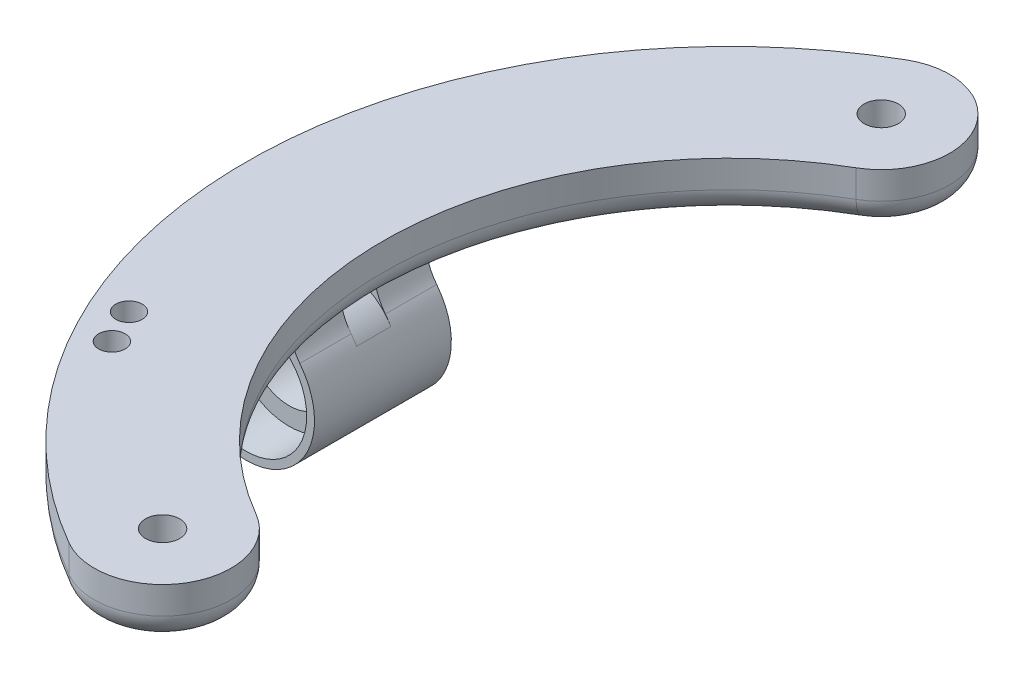
SolidWorks part; units mm, degrees
ref_plane "Front Plane" through (0, 0, 0) normal (0, 0, 1) x (1, 0, 0)
ref_plane "Top Plane" through (0, 0, 0) normal (0, 1, 0) x (1, 0, 0)
ref_plane "Right Plane" through (0, 0, 0) normal (1, 0, 0) x (0, 0, -1)
sketch "Sketch1" plane through (0, 0, 0) normal (0, 0, 1) x (1, 0, 0)
  line L0 (0, -6.6146) -> (0, 6.6146) construction
  line L1 (-64.2938, 0) -> (-64.2938, -5.08)
  line L2 (-69.0563, -9.8425) -> (-84.9312, -9.8425)
  line L3 (-89.6937, -5.08) -> (-89.6937, 0)
  line L4 (-89.6937, 0) -> (-64.2938, 0)
  line L5 (64.4709, -12.0559) -> (-64.2938, -9.8425) construction
  arc A0 (-84.9312, -9.8425) -> (-89.6937, -5.08) centre (-84.9312, -5.08) cw
  arc A1 (-69.0563, -9.8425) -> (-64.2938, -5.08) centre (-69.0563, -5.08) ccw
  point P4 (0, 0)
  point P12 (-89.6937, -9.8425)
  dimension "D4" = 4.7625
  dimension "D1" = 25.4
  dimension "D2" = 9.8425
  dimension "D3" = 128.5875
revolve "MainAttachmentRing" add sketch "Sketch1" angle 360 about L0
sketch "Sketch2" plane through (0, 0, 0) normal (0, 0, 1) x (1, 0, 0)
  line L5 (-76.9938, -9.8425) -> (-76.9938, -22.5425) construction
  line L6 (-76.9938, -22.5425) -> (-76.9938, -39.878) construction
  line L7 (0, 0) -> (0, -9.8425) construction
  line L8 (0, -9.8425) -> (-76.9938, -9.8425) construction
  line L9 (-69.0563, -8.7943) -> (-69.0563, -3.4925)
  line L10 (-69.0563, -9.8425) -> (-84.9312, -9.8425) construction
  line L11 (-84.9312, -8.7943) -> (-84.9312, -3.4925)
  line L13 (-69.0563, -9.8425) -> (69.0563, -9.8425) construction
  line L14 (-69.0563, -9.8425) -> (69.0563, -9.8425) construction
  line L18 (-84.9312, -9.8425) -> (84.9312, -9.8425) construction
  line L19 (-84.9312, -9.8425) -> (84.9312, -9.8425) construction
  line L20 (-69.0563, -3.4925) -> (-84.9312, -3.4925)
  line L21 (-84.9312, -31.9405) -> (-84.9312, -24.325) construction
  line L22 (-84.9312, -24.325) -> (-84.9312, -23.2606) construction
  line L24 (-69.0563, -24.325) -> (-69.0563, -23.2606) construction
  line L25 (-84.9312, -23.2606) -> (-84.9312, -12.6286) construction
  line L26 (-69.0563, -23.2606) -> (-69.0563, -12.6286) construction
  circle A2 centre (-76.9938, -22.5425) radius 2.3813 construction
  arc A5 (-86.9723, -14.6864) -> (-67.0152, -14.6864) centre (-76.9938, -22.5425) ccw
  circle A6 centre (-76.9938, -22.5425) radius 8.1352 construction
  arc A7 (-69.0563, -12.6286) -> (-76.9938, -9.8425) centre (-76.9938, -22.5425) ccw construction
  circle A8 centre (-76.9938, -22.5425) radius 7.9375
  arc A9 (-76.9938, -9.8425) -> (-84.9312, -12.6286) centre (-76.9938, -22.5425) ccw construction
  arc A10 (-69.0563, -8.7943) -> (-67.0152, -14.6864) centre (-59.5313, -8.7943) ccw
  arc A11 (-84.9312, -8.7943) -> (-86.9723, -14.6864) centre (-94.4562, -8.7943) cw
  circle A12 centre (-76.9938, -22.5425) radius 4 construction
  dimension "D3" = 15.875
  dimension "D4" = 4.7625
  dimension "D6" = 9.525
  dimension "D5" = 8
  dimension "D7" = 12.7
  dimension "D1" = 6.35
  dimension "D2" = 12.7
extrude "SensorArmature" add sketch "Sketch2" along normal blind 12.7 and the other way blind 12.7 contours L11 A11 A5 A10 L9 L20 A12 region at (-68.9157, -12.0452, 0)
sketch "Sketch15" plane through (0, 0, 12.7) normal (0, 0, 1) x (1, 0, 0)
  circle A0 centre (-76.9938, -22.5425) radius 11.25
  dimension "D1" = 22.5
extrude "BearingRace1" cut sketch "Sketch15" against normal blind 8
sketch "Sketch16" plane through (0, 0, -12.7) normal (0, 0, -1) x (-1, 0, 0)
  circle A0 centre (76.9938, -22.5425) radius 11.25 construction
  circle A1 centre (76.9938, -22.5425) radius 11.25
extrude "BearingRace2" cut sketch "Sketch16" against normal blind 8
sketch "Sketch6" plane through (0, 0, 0) normal (0, 1, 0) x (1, 0, 0)
  line L0 (0, 0) -> (38.4252, 0) construction
  line L1 (68.0638, -50.8) -> (128.8023, -50.8)
  line L2 (66.0722, 0) -> (128.8023, 0) construction
  line L3 (66.0722, -53.3646) -> (66.0722, -20.0805)
  line L4 (68.0638, 50.8) -> (128.8023, 50.8)
  line L5 (128.8023, -50.8) -> (128.8023, 50.8)
  line L6 (66.0722, -20.0805) -> (66.0722, 0) construction
  line L7 (66.0722, 20.0805) -> (66.0722, 53.3646)
  line L8 (66.0722, 0) -> (66.0722, 20.0805) construction
  line L9 (66.0722, 53.3646) -> (66.0722, 60.6583) construction
  line L10 (66.0722, -60.6583) -> (66.0722, -53.3646) construction
  circle A0 centre (0, 0) radius 69.0563 construction
  circle A1 centre (0, 0) radius 89.6937 construction
  arc A2 (66.0722, -20.0805) -> (66.0722, 20.0805) centre (0, 0) ccw
  arc A3 (0, 69.0563) -> (66.0722, -20.0805) centre (0, 0) ccw construction
  arc A4 (66.0722, 20.0805) -> (0, 69.0563) centre (0, 0) ccw construction
  circle A5 centre (0, 0) radius 84.9312 construction
  arc A6 (68.0638, -50.8) -> (66.0722, -53.3646) centre (0, 0) ccw
  arc A7 (84.9312, 0) -> (66.0722, 53.3646) centre (0, 0) ccw construction
  arc A8 (66.0722, 53.3646) -> (68.0638, 50.8) centre (0, 0) ccw
  arc A9 (66.0722, -53.3646) -> (84.9312, 0) centre (0, 0) ccw construction
  arc A10 (0, 84.9312) -> (68.0638, -50.8) centre (0, 0) ccw construction
  arc A11 (68.0638, 50.8) -> (0, 84.9312) centre (0, 0) ccw construction
  dimension "D1" = 101.6
  dimension "D2" = 63.5
sketch "Sketch17" plane through (65.0875, 22.225, 0) normal (-1, 0, 0) x (0, 0, 1)
  line L0 (2.8259, -32.0675) -> (3.175, -32.0675)
  line L1 (3.175, -32.0675) -> (3.175, -33.655)
  line L2 (3.175, -33.655) -> (-3.175, -33.655)
  line L3 (-3.175, -33.655) -> (-3.175, -32.0675)
  line L4 (-3.175, -32.0675) -> (-2.8259, -32.0675)
  spline S0 degree 3 poles (-1002.8259, -32.0675) (-334.276, -32.0675) (334.2739, -32.0675) (1002.8237, -32.0675) knots -176.932162 -176.932162 -176.932162 -176.932162 177.931775 177.931775 177.931775 177.931775 only from (-2.8259, -32.0675) to (2.8259, -32.0675) construction
  spline S1 degree 3 poles (-2.8259, -32.0675) (-0.942, -32.0675) (0.942, -32.0675) (2.8259, -32.0675) knots 0 0 0 0 1 1 1 1
  dimension "D1" = 1.5875
  dimension "D2" = 6.35
extrude "Cut-Extrude3" cut sketch "Sketch17" along normal through all
fillet "Fillet1" radius 9.525 2 edges at (-85.3032, -11.43, 0) (-68.6843, -11.43, 0)
sketch "Sketch19" plane through (0, -9.8425, 0) normal (0, -1, 0) x (1, 0, 0)
  line L0 (-76.4874, 12.7) -> (-76.4874, -12.7) construction
  line L1 (-83.9763, 12.7) -> (-68.9984, 12.7) construction
  line L2 (-83.9763, -12.7) -> (-68.9984, -12.7) construction
  line L3 (-83.9763, 12.7) -> (-68.9984, 12.7) construction
  line L4 (-83.9763, 15.875) -> (-68.9984, 15.875)
  line L5 (-83.9763, 28.575) -> (-78.6026, 28.575)
  line L6 (-76.4874, 15.875) -> (-76.4874, 28.575) construction
  line L7 (-83.9763, 15.875) -> (-83.9763, 28.575)
  line L8 (-68.9984, 23.6461) -> (-68.9984, 15.875)
  line L9 (-68.9984, 28.575) -> (-68.9984, 24.7775) construction
  line L10 (-70.9492, 28.575) -> (-68.9984, 28.575) construction
  line L11 (-83.9763, 28.575) -> (-68.9984, 28.575) construction
  line L12 (-74.361, 28.575) -> (-70.9492, 28.575) construction
  circle A0 centre (0, 0) radius 76.4874 construction
  arc A1 (-62.0003, 39.1237) -> (-67.3705, 42.5124) centre (-64.6854, 40.818) ccw
  arc A2 (-67.3705, 42.5124) -> (-72.7997, 32.3466) centre (0, 0) ccw
  arc A3 (-62.0003, 39.1237) -> (-68.5893, 25.8884) centre (0, 0) ccw
  arc A4 (-78.6435, 12.7) -> (-67.3705, 42.5124) centre (0, 0) ccw construction
  circle A5 centre (0, 0) radius 79.6624 construction
  arc A6 (-72.204, 12.7) -> (-62.0003, 39.1237) centre (0, 0) ccw construction
  circle A7 centre (0, 0) radius 73.3124 construction
  arc A8 (-68.9984, 24.7775) -> (-71.573, 15.875) centre (0, 0) ccw construction
  arc A9 (-71.573, 15.875) -> (-72.204, 12.7) centre (0, 0) ccw construction
  arc A10 (-74.361, 28.575) -> (-76.4874, 22.266) centre (0, 0) ccw construction
  arc A11 (-76.4874, 22.266) -> (-78.0646, 15.875) centre (0, 0) ccw construction
  arc A12 (-78.0646, 15.875) -> (-78.6435, 12.7) centre (0, 0) ccw construction
  arc A13 (-66.3237, 38.0983) -> (-62.0003, 39.1237) centre (-64.6854, 40.818) ccw construction
  arc A14 (-67.3705, 42.5124) -> (-66.3237, 38.0983) centre (-64.6854, 40.818) ccw construction
  arc A15 (-72.7997, 32.3466) -> (-78.6026, 28.575) centre (-78.6026, 34.925) cw
  arc A16 (-68.5893, 25.8884) -> (-68.9984, 23.6461) centre (-62.6484, 23.6461) ccw
  point P9 (-76.4874, 0)
  dimension "D3" = 6.35
  dimension "D6" = 6.35
  dimension "D8" = 152.9748
  dimension "D7" = 28.118
  dimension "D1" = 3.175
  dimension "D2" = 12.7
  dimension "D4" = 3.175
  dimension "D5" = 3.175
extrude "MainSensorInset" cut sketch "Sketch19" against normal blind 6.35
hole_wizard "#10 (0.1935) Diameter Hole1" positions "Sketch25" profile "Sketch24" hole size "#10" standard "ANSI Inch" end condition through all
sketch "Sketch25" plane through (0, -9.8425, 0) normal (0, -1, 0) x (-1, 0, 0)
  line L0 (83.9763, -28.575) -> (83.9763, -15.875) construction
  line L1 (83.9763, -28.575) -> (83.9763, -15.875) construction
  line L2 (83.9763, -15.875) -> (68.9984, -15.875) construction
  line L3 (83.9763, -15.875) -> (68.9984, -15.875) construction
  line L4 (76.4874, -15.875) -> (76.4874, -34.925) construction
  line L6 (83.9763, -28.575) -> (76.4874, -28.575) construction
  line L7 (76.4874, -28.575) -> (73.3124, -28.575) construction
  line L8 (73.3124, -28.575) -> (73.3124, -41.275) construction
  point P0 (73.3124, -41.275)
  point P2 (76.4874, -34.925)
  dimension "D1" = 19.05
  dimension "D2" = 12.7
  dimension "D3" = 3.175
sketch "Sketch24" plane through (-73.3124, -9.8425, 41.275) normal (1, 0, 0) x (0, 0, -1)
  line L0 (0, 0) -> (0, 9.8425)
  line L1 (0, 9.8425) -> (2.4574, 9.8425)
  line L2 (2.4574, 9.8425) -> (2.4574, 0)
  line L5 (2.4574, 0) -> (0, 0)
  line L11 (0, -6.35) -> (0, 107.95) construction
  dimension "Thru Hole Dia." = 4.9149
  dimension "Thru Hole Depth" = 9.8425
hole_wizard "1/4 (0.25) Diameter Hole1" positions "Sketch26" profile "Sketch27" hole size "1/4" standard "ANSI Inch" end condition through all
sketch "Sketch26" plane through (0, -9.8425, 0) normal (0, -1, 0) x (-1, 0, 0)
  line L0 (0, 0) -> (-76.9938, 0) construction
  arc A3 (76.9293, 3.1508) -> (76.9293, -3.1508) centre (0, 0) ccw
  arc A4 (76.9293, 3.1508) -> (76.9293, -3.1508) centre (0, 0) ccw construction
  point P0 (-76.9938, 0)
  point P30 (38.4969, 66.6785)
  point P31 (38.4969, -66.6785)
  point P32 (0, 0)
  dimension "D1" = 7.9375
  dimension "D2" = 3
sketch "Sketch27" plane through (76.9938, -9.8425, 0) normal (1, 0, 0) x (0, 0, -1)
  line L0 (0, 0) -> (0, 9.8425)
  line L1 (0, 9.8425) -> (3.175, 9.8425)
  line L2 (3.175, 9.8425) -> (3.175, 0.635)
  line L3 (3.175, 0.635) -> (3.81, 0)
  line L5 (3.81, 0) -> (0, 0)
  line L6 (-3.175, 0.635) -> (-3.81, 0) construction
  line L11 (0, -6.35) -> (0, 107.95) construction
  dimension "Thru Hole Dia." = 6.35
  dimension "Thru Hole Depth" = 9.8425
  dimension "Near C'Sink Dia." = 7.62
  dimension "Near C'Sink Angle" = 90
sketch "Sketch28" plane through (0, 0, 0) normal (0, 1, 0) x (1, 0, 0)
  line L0 (0, 0) -> (-32.1469, 55.68)
  line L1 (-52.6413, 91.1774) -> (62.9712, 117.188)
  line L2 (62.9712, 117.188) -> (148.9034, 11.6303)
  line L3 (148.9034, 11.6303) -> (-6.9891, -155.4639)
  line L4 (-6.9891, -155.4639) -> (-55.4139, -95.9797)
  line L5 (-55.4139, -95.9797) -> (-44.8469, -77.6771)
  line L6 (-38.4969, -66.6785) -> (-32.1469, -55.68) construction
  line L7 (-32.1469, -55.68) -> (0, 0)
  line L8 (-44.8469, -77.6771) -> (-38.4969, -66.6785) construction
  line L9 (-32.1469, 55.68) -> (-38.4969, 66.6785) construction
  line L10 (-44.8469, 77.6771) -> (-52.6413, 91.1774)
  line L11 (-38.4969, 66.6785) -> (-44.8469, 77.6771) construction
  circle A2 centre (0, 0) radius 76.9937
  circle A3 centre (0, 0) radius 76.9937 construction
  arc A4 (-32.1469, 55.68) -> (-44.8469, 77.6771) centre (-38.4969, 66.6785) ccw
  arc A5 (-44.8469, -77.6771) -> (-32.1469, -55.68) centre (-38.4969, -66.6785) ccw
  arc A6 (-32.1469, -55.68) -> (-48.9342, -59.4431) centre (-38.4969, -66.6785) ccw construction
  arc A7 (-48.9342, -59.4431) -> (-44.8469, -77.6771) centre (-38.4969, -66.6785) ccw construction
  arc A8 (-44.8469, 77.6771) -> (-48.9342, 59.4431) centre (-38.4969, 66.6785) ccw construction
  arc A9 (-48.9342, 59.4431) -> (-32.1469, 55.68) centre (-38.4969, 66.6785) ccw construction
  dimension "D1" = 12.7
extrude "Cut-Extrude6" cut sketch "Sketch28" against normal through all both and the other way through all
fillet "Fillet2" radius 4.7625 2 edges at (-27.1119, -9.8425, 72.3063) (-27.1119, -9.8425, -72.3063)
